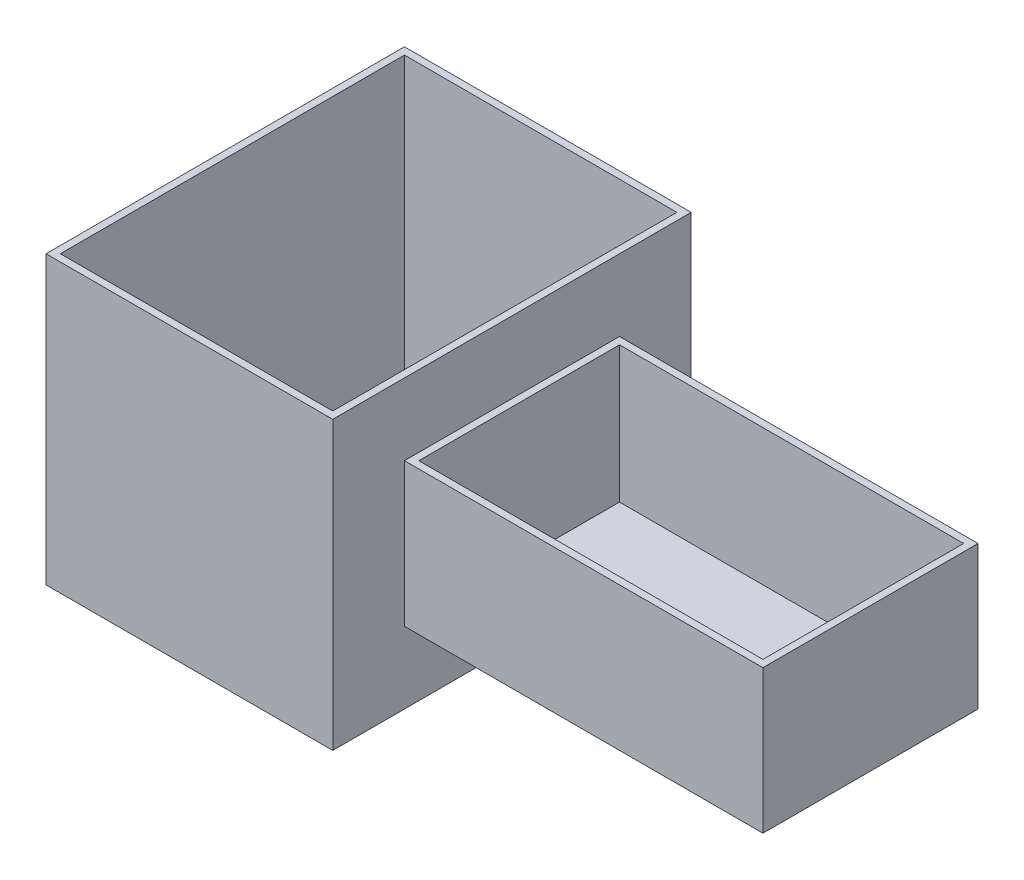
SolidWorks part; units mm, degrees
material "Glass"
ref_plane "Front Plane" through (0, 0, 0) normal (0, 0, 1) x (1, 0, 0)
ref_plane "Top Plane" through (0, 0, 0) normal (0, 1, 0) x (1, 0, 0)
ref_plane "Right Plane" through (0, 0, 0) normal (1, 0, 0) x (0, 0, -1)
sketch "Sketch1" plane through (0, 0, 0) normal (0, 1, 0) x (1, 0, 0)
  line L1 (50.8, 63.5) -> (-50.8, 63.5)
  line L2 (50.8, 63.5) -> (50.8, -63.5)
  line L3 (50.8, -63.5) -> (-50.8, -63.5)
  line L4 (-50.8, 63.5) -> (-50.8, -63.5)
  line L5 (50.8, 63.5) -> (-50.8, -63.5) construction
  line L6 (50.8, -63.5) -> (-50.8, 63.5) construction
  point P0 (0, 0)
  dimension "D1" = 127
  dimension "D2" = 101.6
extrude "Extrude-Thin1" add sketch "Sketch1" along normal blind 101.6 thin thin type one direction reverse wall 2.54
extrude "Boss-Extrude1" add sketch "Sketch1<2>" along normal blind 2.54
sketch "Sketch1<2>" plane through (0, 0, 0) normal (0, 1, 0) x (1, 0, 0) same geometry as "Sketch1"
ref_plane "Plane1" through (0, 25.4, 0) normal (0, -1, 0) x (-1, 0, 0)
sketch "Sketch2" plane through (0, 25.4, 0) normal (0, 1, 0) x (1, 0, 0)
  line L0 (50.8, -63.5) -> (50.8, 63.5) construction
  line L1 (50.8, 38.1) -> (177.8, 38.1)
  line L2 (50.8, 38.1) -> (50.8, -38.1)
  line L3 (50.8, -38.1) -> (177.8, -38.1)
  line L4 (177.8, 38.1) -> (177.8, -38.1)
  point P6 (50.8, 0)
  dimension "D1" = 76.2
  dimension "D2" = 127
extrude "Extrude-Thin2" add sketch "Sketch2" along normal blind 50.8 thin thin type one direction reverse wall 2.54
extrude "Boss-Extrude2" add sketch "Sketch2<2>" along normal blind 2.54
sketch "Sketch2<2>" plane through (0, 25.4, 0) normal (0, 1, 0) x (1, 0, 0) same geometry as "Sketch2"
